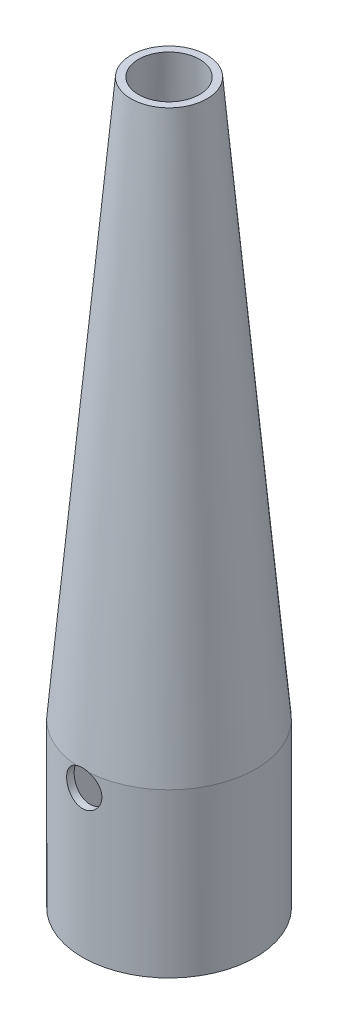
SolidWorks part; units mm, degrees
material "S-Glass Fiber"
ref_plane "Front Plane" through (0, 0, 0) normal (0, 0, 1) x (1, 0, 0)
ref_plane "Top Plane" through (0, 0, 0) normal (0, 1, 0) x (1, 0, 0)
ref_plane "Right Plane" through (0, 0, 0) normal (1, 0, 0) x (0, 0, -1)
sketch "Sketch1" plane through (0, 0, 0) normal (0, 0, 1) x (1, 0, 0)
  line L0 (0, 0) -> (0, 53.5349) construction
  line L1 (9.525, 53.5349) -> (11.8197, 53.5349)
  line L2 (11.8197, 53.5349) -> (26.9875, -119.8334)
  line L3 (26.9875, -119.8334) -> (24.6928, -119.8334)
  line L4 (24.6928, -119.8334) -> (9.525, 53.5349)
  line L6 (24.6928, -119.8334) -> (26.9875, -119.8334)
  line L7 (24.6928, -119.8334) -> (24.6928, -170.6334)
  line L8 (24.6928, -170.6334) -> (26.9875, -170.6334)
  line L9 (26.9875, -119.8334) -> (26.9875, -170.6334)
  line L10 (26.9875, -170.6334) -> (26.9875, -919.9334) construction
revolve "Revolve1" add sketch "Sketch1" angle 360 about L0 region at (18.2563, -33.1493, 0) region at (25.8401, -145.2334, 0)
sketch "Sketch2" plane through (0, 0, 0) normal (0, 0, 1) x (1, 0, 0)
  line L0 (0, 53.5349) -> (0, -124.9651) construction
  line L1 (-11.8197, 53.5349) -> (11.8197, 53.5349) construction
  circle A0 centre (0, -124.9651) radius 5.5
  dimension "D1" = 11
  dimension "D2" = 178.5
extrude "Cut-Extrude1" cut sketch "Sketch2" along normal through all
